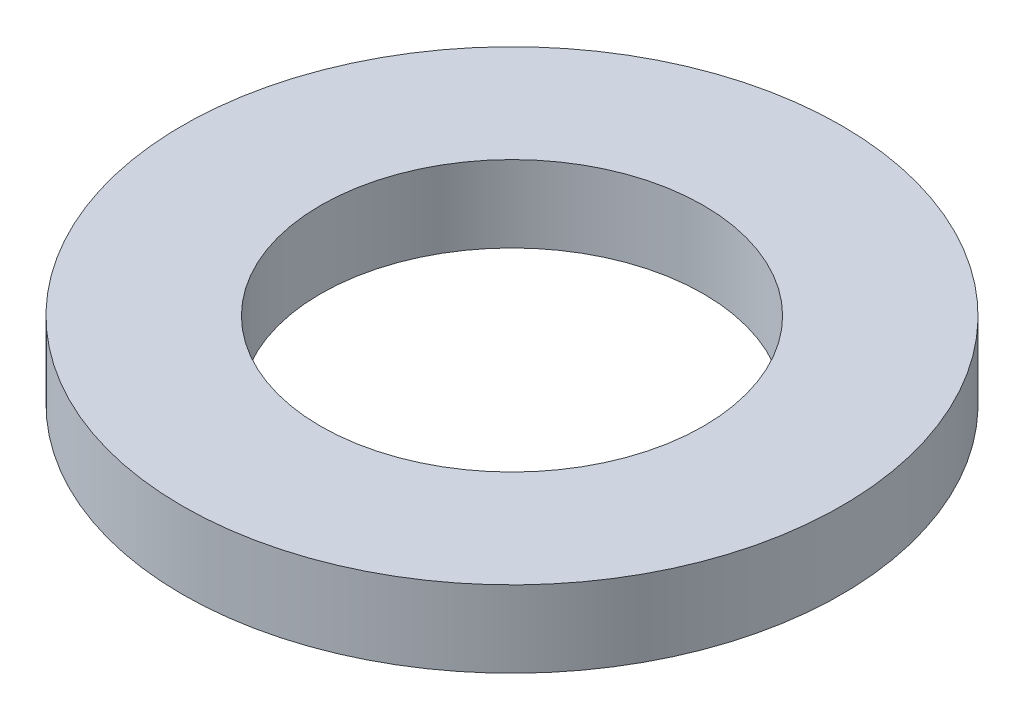
SolidWorks part; units mm, degrees
ref_plane "Front Plane" through (0, 0, 0) normal (0, 0, 1) x (1, 0, 0)
ref_plane "Top Plane" through (0, 0, 0) normal (0, 1, 0) x (1, 0, 0)
ref_plane "Right Plane" through (0, 0, 0) normal (1, 0, 0) x (0, 0, -1)
sketch "Sketch1" plane through (0, 0, 0) normal (0, 1, 0) x (1, 0, 0)
  circle A0 centre (0, 0) radius 77.5
  dimension "FLANGE_OD" = 155
extrude "Boss-Extrude1" add sketch "Sketch1" along normal blind 18
sketch "Sketch2" plane through (0, 0, 0) normal (0, 1, 0) x (1, 0, 0)
  circle A0 centre (0, 0) radius 45
  dimension "BORE_D" = 90
extrude "Cut-Extrude1" cut sketch "Sketch2" along normal through all
sketch "Sketch3" plane through (0, 18, 0) normal (0, 1, 0) x (1, 0, 0)
  circle A0 centre (0, 0) radius 34.8079 construction
  circle A1 centre (-34.8079, 0) radius 4.79
  dimension "BOLT_D" = 9.5801
  dimension "BOLT_PCD" = 69.6158
extrude "Cut-Extrude2" cut sketch "Sketch3" against normal blind 14.3775 rebuild error yes
pattern_circular "CirPattern1" count 8 over 360 rebuild error yes
